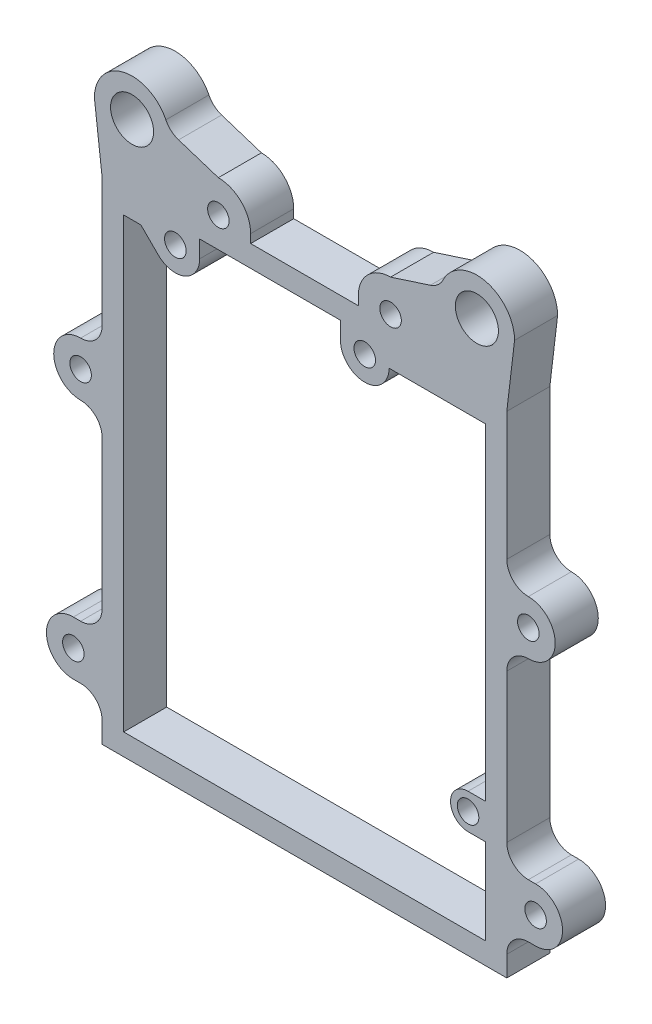
SolidWorks part; units mm, degrees
ref_plane "Front Plane" through (0, 0, 0) normal (0, 0, 1) x (1, 0, 0)
ref_plane "Top Plane" through (0, 0, 0) normal (0, 1, 0) x (1, 0, 0)
ref_plane "Right Plane" through (0, 0, 0) normal (1, 0, 0) x (0, 0, -1)
sketch "Sketch1" plane through (0, 0, 0) normal (0, 0, 1) x (1, 0, 0)
  line L0 (13.97, -3.175) -> (39.37, -3.175)
  line L2 (39.37, -3.175) -> (56.515, -3.175)
  line L3 (18.7325, 73.025) -> (18.7325, 71.755)
  line L4 (56.515, 69.215) -> (41.6251, 77.2198)
  line L5 (34.6075, 73.025) -> (34.6075, 71.755)
  line L6 (-3.175, 69.215) -> (11.7149, 77.2198)
  line L7 (34.6075, 71.755) -> (18.7325, 71.755)
  line L8 (0, 11.0938) -> (0, 16.5575)
  line L36 (53.34, 66.04) -> (53.34, 0) construction
  line L37 (53.34, 0) -> (0, 0) construction
  line L38 (0, 0) -> (0, 66.04) construction
  line L39 (0, 66.04) -> (2.54, 66.04) construction
  line L43 (40.386, 66.04) -> (53.34, 66.04) construction
  line L44 (-3.175, -3.175) -> (56.515, -3.175)
  line L45 (56.515, -3.175) -> (56.515, 69.215)
  line L46 (-3.175, 69.215) -> (-3.175, -3.175)
  line L47 (1.2249, 69.215) -> (-3.175, 69.215)
  line L48 (3.7649, 71.755) -> (1.2249, 69.215)
  line L49 (39.1611, 71.755) -> (3.7649, 71.755)
  line L50 (41.7011, 69.215) -> (39.1611, 71.755)
  line L51 (56.515, 69.215) -> (41.7011, 69.215)
  line L52 (-3.175, -3.175) -> (13.97, -3.175)
  line L53 (56.515, -3.175) -> (56.515, 69.215)
  line L54 (-3.175, 69.215) -> (-3.175, -3.175)
  line L60 (53.34, 66.04) -> (53.34, 17.8275)
  line L61 (53.34, 0) -> (0, 0)
  line L62 (0, 0) -> (0, 11.0938)
  line L63 (0, 66.04) -> (2.54, 66.04)
  line L64 (26.67, -3.175) -> (26.67, 77.2177) construction
  line L66 (11.2075, 68.58) -> (31.9725, 68.58)
  line L67 (40.386, 66.04) -> (53.34, 66.04)
  line L68 (50.8, 17.8275) -> (53.34, 17.8275)
  line L69 (50.8, 12.6525) -> (53.34, 12.6525)
  line L70 (53.34, 12.6525) -> (53.34, 0)
  line L74 (0, 16.5575) -> (0, 66.04)
  line L75 (5.08, 63.5065) -> (2.54, 66.04)
  line L76 (11.2075, 66.04) -> (11.2075, 68.58)
  line L77 (39.1475, 66.04) -> (40.386, 66.04)
  line L78 (31.9725, 66.04) -> (31.9725, 68.58)
  circle A0 centre (35.56, 66.04) radius 1.5875 construction
  circle A1 centre (7.62, 66.04) radius 1.5875 construction
  circle A3 centre (50.8, 15.24) radius 1.5875 construction
  circle A4 centre (35.56, 66.04) radius 1.5875
  circle A5 centre (7.62, 66.04) radius 1.5875
  circle A7 centre (50.8, 15.24) radius 1.5875
  arc A9 (50.8, 17.8275) -> (50.8, 12.6525) centre (50.8, 15.24) ccw
  arc A10 (5.08, 63.5065) -> (11.2075, 66.04) centre (7.62, 66.04) ccw
  arc A13 (31.9725, 66.04) -> (39.1475, 66.04) centre (35.56, 66.04) ccw
  circle A15 centre (35.56, 66.04) radius 3.5875 construction
  circle A16 centre (7.62, 66.04) radius 3.5875 construction
  circle A18 centre (39.37, 73.025) radius 1.5875
  arc A19 (41.6251, 77.2198) -> (34.6075, 73.025) centre (39.37, 73.025) ccw
  circle A20 centre (13.97, 73.025) radius 1.5875
  arc A22 (11.7149, 77.2198) -> (18.7325, 73.025) centre (13.97, 73.025) cw
  circle A24 centre (13.97, 73.025) radius 4.7625 construction
  point P20 (2.54, 13.97)
  point P29 (2.54, 13.97)
  point P34 (53.3875, 15.24)
  point P37 (6.1275, 13.97)
  point P41 (4.0581, 14.4341)
  point P47 (11.2075, 66.04)
  point P54 (39.1475, 66.04)
  point P58 (26.67, -9.525)
  point P64 (31.4325, -9.525)
  point P65 (26.67, -6.35)
  point P69 (26.67, 71.755)
  point P71 (39.37, 73.025)
  point P74 (50.4825, 73.025)
  point P75 (12.3825, 73.025)
  point P78 (31.4325, -6.35)
  dimension "D8" = 3.175
  dimension "D7" = 12.7
  dimension "D9" = 12.7
  dimension "D1" = 3.175
  dimension "D3" = 2
  dimension "D12" = 3.175
extrude "Boss-Extrude1" add sketch "Sketch1" along normal blind 6.35
sketch "Sketch3" plane through (0, 0, 6.35) normal (0, 0, 1) x (1, 0, 0)
  line L0 (26.67, 0) -> (26.67, 68.58) construction
  line L1 (0, 0) -> (53.34, 0) construction
  line L2 (31.9725, 68.58) -> (11.2075, 68.58) construction
  line L3 (-3.175, -3.175) -> (56.515, -3.175) construction
  line L4 (-3.175, 69.215) -> (-3.175, -3.175) construction
  line L5 (-7.4237, 10.9692) -> (-3.175, 10.9692)
  line L6 (-7.4237, 3.0317) -> (-3.175, 3.0317)
  line L7 (-3.175, 3.0317) -> (-3.175, 10.9692)
  line L8 (56.515, 3.0317) -> (56.515, 10.9692)
  line L9 (60.7637, 3.0317) -> (56.515, 3.0317)
  line L10 (60.7637, 10.9692) -> (56.515, 10.9692)
  circle A0 centre (-7.4237, 7.0005) radius 1.5875
  arc A1 (-7.4237, 10.9692) -> (-7.4237, 3.0317) centre (-7.4237, 7.0005) ccw
  arc A2 (60.7637, 10.9692) -> (60.7637, 3.0317) centre (60.7637, 7.0005) cw
  circle A3 centre (60.7637, 7.0005) radius 1.5875
  dimension "D1" = 3.175
  dimension "D2" = 10.1755
  dimension "D3" = 4.2487
extrude "Boss-Extrude2" add sketch "Sketch3" against normal up to surface (6.35 mm away) up to face at (26.67, 58.006, 0)
fillet "Fillet1" radius 3.175 4 edges
sketch "Sketch4" plane through (0, 0, 6.35) normal (0, 0, 1) x (1, 0, 0)
  line L0 (26.67, 0) -> (26.67, 68.58) construction
  line L1 (0, 0) -> (53.34, 0) construction
  line L2 (31.9725, 68.58) -> (11.2075, 68.58) construction
  line L3 (-3.175, 69.215) -> (-3.175, 14.1442) construction
  line L4 (-6.35, 47.1371) -> (-3.175, 47.1371)
  line L5 (-6.35, 39.1996) -> (-3.175, 39.1996)
  line L6 (-3.175, 39.1996) -> (-3.175, 47.1371)
  line L7 (56.515, 39.1996) -> (56.515, 47.1371)
  line L8 (59.69, 39.1996) -> (56.515, 39.1996)
  line L9 (59.69, 47.1371) -> (56.515, 47.1371)
  line L10 (4.27, 73.2174) -> (-3.175, 87.066) construction
  line L11 (11.7149, 77.2198) -> (-3.175, 69.215) construction
  line L12 (49.07, 73.2174) -> (56.515, 87.066) construction
  line L13 (-4.3181, 78.857) -> (-3.175, 69.215)
  line L14 (6.6403, 80.1562) -> (13.97, 77.7875)
  line L15 (-3.175, 69.215) -> (13.97, 77.7875)
  line L16 (56.515, 69.215) -> (39.37, 77.7875)
  line L17 (46.6997, 80.1562) -> (39.37, 77.7875)
  line L18 (57.6581, 78.857) -> (56.515, 69.215)
  circle A0 centre (-6.35, 43.1684) radius 1.5875
  arc A1 (-6.35, 47.1371) -> (-6.35, 39.1996) centre (-6.35, 43.1684) ccw
  arc A2 (59.69, 47.1371) -> (59.69, 39.1996) centre (59.69, 43.1684) cw
  circle A3 centre (59.69, 43.1684) radius 1.5875
  circle A4 centre (1.2381, 78.857) radius 3.175
  arc A5 (6.6403, 80.1562) -> (-4.1641, 77.5578) centre (1.2381, 78.857) ccw
  arc A6 (18.7325, 73.025) -> (11.7149, 77.2198) centre (13.97, 73.025) ccw construction
  arc A7 (46.6997, 80.1562) -> (57.5041, 77.5578) centre (52.1019, 78.857) cw
  circle A8 centre (52.1019, 78.857) radius 3.175
  line M20 (-3.175, 69.215) -> (-3.175, 14.1442)
  line M34 (56.515, 14.1442) -> (56.515, 69.215)
  line M35 (56.515, 69.215) -> (41.6251, 77.2198)
  arc M36 (41.6251, 77.2198) -> (34.6075, 73.025) centre (39.37, 73.025) ccw
  arc M40 (18.7325, 73.025) -> (11.7149, 77.2198) centre (13.97, 73.025) ccw
  line M41 (11.7149, 77.2198) -> (-3.175, 69.215)
  dimension "D1" = 3.175
  dimension "D2" = 3.175
  dimension "D3" = 6.35
  dimension "D4" = 11.1125
extrude "Boss-Extrude3" add sketch "Sketch4" against normal up to surface (6.35 mm away) contours L14 A5 L13 A4 M41 M40 | A7 L17 L18 A8 M36 M35 | A2 L9 L8 A3 M34 | L4 A1 L5 A0 M20 region at (-3.4334, 73.4144, 6.35) region at (-4.7625, 47.0304, 6.35) region at (49.1826, 73.4268, 6.35) region at (56.6218, 43.1684, 6.35) up to face at (26.67, 30.1848, 0)
fillet "Fillet2" radius 3.175 6 edges at (46.6997, 80.1562, 3.175) (6.6403, 80.1562, 3.175) (-3.175, 47.1371, 3.175) (56.515, 47.1371, 3.175) (56.515, 39.1996, 3.175) (-3.175, 39.1996, 3.175)
